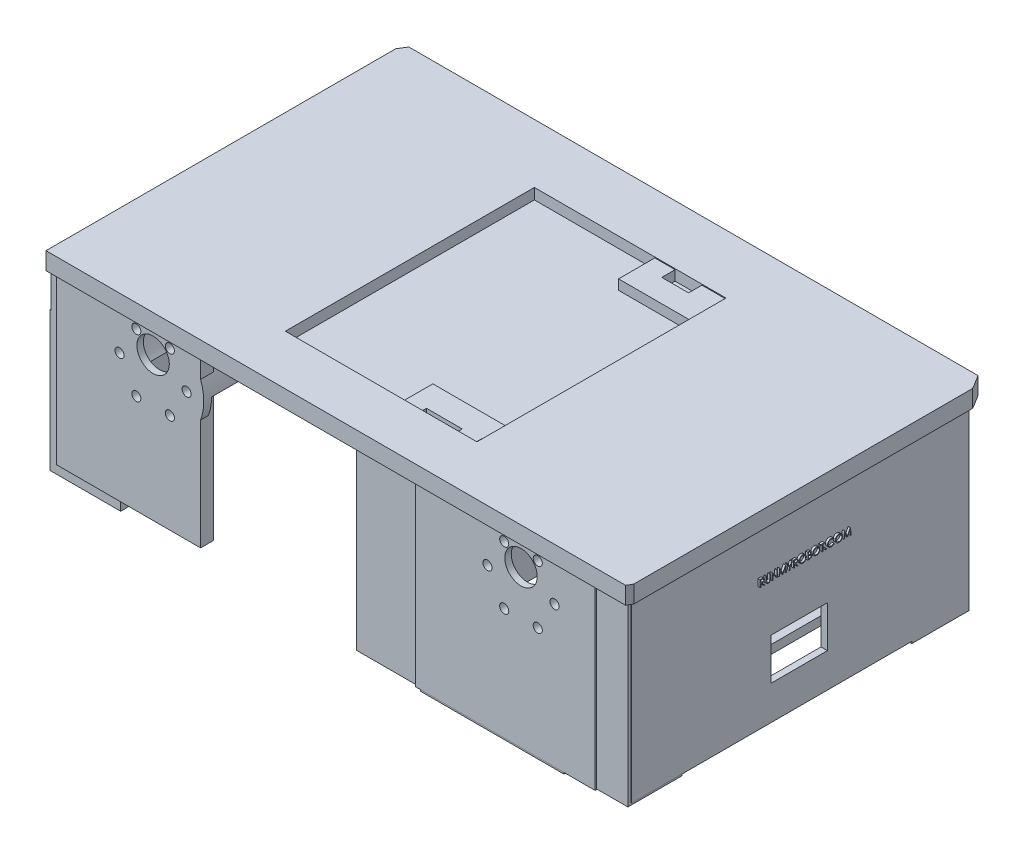
SolidWorks part; units mm, degrees
ref_plane "Front Plane" through (0, 0, 0) normal (0, 0, 1) x (1, 0, 0)
ref_plane "Top Plane" through (0, 0, 0) normal (0, 1, 0) x (1, 0, 0)
ref_plane "Right Plane" through (0, 0, 0) normal (1, 0, 0) x (0, 0, -1)
sketch "MotorHoldersSketch" plane through (0, 0, 0) normal (0, 0, 1) x (1, 0, 0)
  line L0 (0, 0) -> (170, 0) construction
  line L1 (0, 0) -> (0, 23.41) construction
  line L2 (170, 0) -> (170, 23.41) construction
  circle A0 centre (0, 0) radius 23.41
  circle A1 centre (170, 0) radius 23.41
ref_axis "MotorCenterAxis1" through (0, 0, 0) along (0, 0, 1)
ref_axis "MotorCenterAxis2" through (170, 0, 0) along (0, 0, 1)
extrude "MotorHolders" add sketch "MotorHoldersSketch" along normal blind 80 and the other way blind 80
sketch "Sketch3" plane through (0, 0, 0) normal (0, 0, 1) x (1, 0, 0)
  line L1 (1.9406, 21.133) -> (168.3435, 21.133)
  line L2 (1.9406, 21.133) -> (1.9406, 18.3155)
  line L3 (1.9406, 18.3155) -> (168.3435, 18.3155)
  line L4 (168.3435, 21.133) -> (168.3435, 18.3155)
sketch "Sketch4" plane through (0, 0, 0) normal (0, 1, 0) x (1, 0, 0)
  line L1 (221.2811, -76.3794) -> (-41.4939, -76.3794)
  line L2 (221.2811, -76.3794) -> (221.2811, 76.7331)
  line L3 (221.2811, 76.7331) -> (-41.4939, 76.7331)
  line L4 (-41.4939, -76.3794) -> (-41.4939, 76.7331)
extrude "Cut-Extrude1" cut sketch "Sketch4" against normal blind 26
ref_axis "Axis3" through (170, 0, 0) along (0, -1, 0)
sketch3d "ReferencePlanePosition"
  line L0 (170, 0, 0) -> (170, -34.8293, 0)
  line L1 (170, 0, 0) -> (170, -38.994, 0) construction
ref_plane "ReferencePlane" through (170, -34.8293, 0) normal (0, -1, 0) x (-1, 0, 0)
sketch "Sketch6" plane through (170, -34.8293, 0) normal (0, -1, 0) x (-1, 0, 0)
  line L1 (219.5858, 78.949) -> (145.1716, 78.949)
  line L2 (219.5858, 78.949) -> (219.5858, 65.5282)
  line L3 (219.5858, 65.5282) -> (145.1716, 65.5282)
  line L4 (145.1716, 78.949) -> (145.1716, 65.5282)
  line L5 (219.3147, -52.1095) -> (186.667, -52.1095)
  line L6 (219.3147, -52.1095) -> (219.3147, -78.2822)
  line L7 (219.3147, -78.2822) -> (186.667, -78.2822)
  line L8 (186.667, -52.1095) -> (186.667, -78.2822)
  line L9 (75.6651, 77.8627) -> (19.9904, 77.8627)
  line L10 (75.6651, 77.8627) -> (75.6651, 40.7512)
  line L11 (75.6651, 40.7512) -> (19.9904, 40.7512)
  line L12 (19.9904, 77.8627) -> (19.9904, 40.7512)
  line L13 (76.5596, -44.1716) -> (20.0852, -44.1716)
  line L14 (76.5596, -44.1716) -> (76.5596, -79.4437)
  line L15 (76.5596, -79.4437) -> (20.0852, -79.4437)
  line L16 (20.0852, -44.1716) -> (20.0852, -79.4437)
  line L17 (213.765, 73.0364) -> (192.9548, 73.0364)
  line L18 (213.765, 73.0364) -> (213.765, 71.0153)
  line L19 (213.765, 71.0153) -> (192.9548, 71.0153)
  line L20 (192.9548, 73.0364) -> (192.9548, 71.0153)
  line L21 (41.3552, 69.1777) -> (28.5109, 69.1777)
  line L22 (41.3552, 69.1777) -> (41.3552, 50.8413)
  line L23 (41.3552, 50.8413) -> (28.5109, 50.8413)
  line L24 (28.5109, 69.1777) -> (28.5109, 50.8413)
  line L25 (43.3068, -72.8101) -> (32.1723, -72.8101)
  line L26 (43.3068, -72.8101) -> (43.3068, -54.7747)
  line L27 (43.3068, -54.7747) -> (32.1723, -54.7747)
  line L28 (32.1723, -72.8101) -> (32.1723, -54.7747)
  line L29 (211.9411, -70.4881) -> (201.0982, -70.4881)
  line L30 (211.9411, -70.4881) -> (211.9411, -60.1404)
  line L31 (211.9411, -60.1404) -> (201.0982, -60.1404)
  line L32 (201.0982, -70.4881) -> (201.0982, -60.1404)
  line L37 (66.2772, 51.3198) -> (53.8697, 51.3198)
  line L38 (66.2772, 51.3198) -> (66.2772, 67.7632)
  line L39 (66.2772, 67.7632) -> (53.8697, 67.7632)
  line L40 (53.8697, 51.3198) -> (53.8697, 67.7632)
  line L45 (68.2481, -69.8638) -> (51.7107, -69.8638)
  line L46 (68.2481, -69.8638) -> (68.2481, -55.4273)
  line L47 (68.2481, -55.4273) -> (51.7107, -55.4273)
  line L48 (51.7107, -69.8638) -> (51.7107, -55.4273)
  line L49 (-20.7001, -79.4437) -> (-48.8506, -79.4437)
  line L50 (-20.7001, -79.4437) -> (-20.7001, -54.5097)
  line L51 (-20.7001, -54.5097) -> (-48.8506, -54.5097)
  line L52 (-48.8506, -79.4437) -> (-48.8506, -54.5097)
  line L53 (-18.3873, 77.8627) -> (-49.0581, 77.8627)
  line L54 (-18.3873, 77.8627) -> (-18.3873, 51.5325)
  line L55 (-18.3873, 51.5325) -> (-49.0581, 51.5325)
  line L56 (-49.0581, 77.8627) -> (-49.0581, 51.5325)
  line L57 (-41.8141, -72.8101) -> (-31.6362, -72.8101)
  line L58 (-41.8141, -72.8101) -> (-41.8141, -62.9794)
  line L59 (-41.8141, -62.9794) -> (-31.6362, -62.9794)
  line L60 (-31.6362, -72.8101) -> (-31.6362, -62.9794)
  line L61 (-31.6362, 69.1777) -> (-41.5347, 69.1777)
  line L62 (-31.6362, 69.1777) -> (-31.6362, 58.5421)
  line L63 (-31.6362, 58.5421) -> (-41.5347, 58.5421)
  line L64 (-41.5347, 69.1777) -> (-41.5347, 58.5421)
extrude "PowerBankHolders" add sketch "Sketch6" along normal blind 30 and the other way blind 59 separate body
sketch3d "3DSketch3"
  line L0 (170, 0, 0) -> (170, -64.5, 0) construction
ref_plane "Plane2" through (170, -64.5, 0) normal (0, -1, 0) x (-1, 0, 0)
sketch "Sketch7" plane through (170, -64.5, 0) normal (0, -1, 0) x (-1, 0, 0)
  line L1 (-9.5047, -80.801) -> (181.32, -80.801)
  line L2 (-9.5047, -80.801) -> (-9.5047, 73.8662)
  line L3 (-9.5047, 73.8662) -> (181.32, 73.8662)
  line L4 (181.32, -80.801) -> (181.32, 73.8662)
  line L5 (151.8712, -54.3972) -> (26.5361, -54.3972)
  line L6 (151.8712, -54.3972) -> (151.8712, 46.2413)
  line L7 (151.8712, 46.2413) -> (26.5361, 46.2413)
  line L8 (26.5361, -54.3972) -> (26.5361, 46.2413)
ref_point "Point1"
ref_point "Point2"
sketch3d "3DSketch11"
  line L0 (0, 0, -80) -> (170, 0, 80) construction
  point P4 (85, 0, 0)
sketch "MotorHolderExtrudeSketch" plane through (0, 0, 0) normal (0, 0, 1) x (1, 0, 0)
  circle A0 centre (170, 0) radius 20.415
  circle A1 centre (0, 0) radius 20.415
  circle A3 centre (0, 0) radius 23.41 construction
  circle A4 centre (170, 0) radius 23.41 construction
ref_point "TopOfMotors"
ref_plane "TangentToTopOfMotors" through (0, -20.415, 0) normal (0, 1, 0) x (1, 0, 0)
ref_axis "Axis4" through (85, 0, 0) along (0, -1, 0)
ref_plane "BottomOfPowerBankRegion" through (0, -20.425, 0) normal (0, 1, 0) x (1, 0, 0)
sketch "Sketch11" plane through (0, -20.425, 0) normal (0, 1, 0) x (1, 0, 0)
  line L0 (-18.9327, 3.7419) -> (188.9327, -3.7419) construction
  line L5 (-18.9327, -64.7581) -> (-18.9327, 72.2419)
  line L6 (188.9327, 63.7581) -> (188.9327, -71.2419)
  line L7 (188.9327, -71.2419) -> (-18.9327, -64.7581)
  line L8 (188.9327, 63.7581) -> (-18.9327, 72.2419)
  circle A0 centre (85, 0) radius 104 construction
ref_point "CenterAtBottomOfPowerBank"
ref_plane "TopOfPowerBankPlane" through (0, -54.425, 0) normal (0, 1, 0) x (1, 0, 0)
sketch "Sketch13" plane through (0, -54.425, 0) normal (0, 1, 0) x (1, 0, 0)
  line L1 (-19.4498, 72.5454) -> (166.1636, 72.5454)
  line L2 (-19.4498, 72.5454) -> (-19.4498, -78.2051)
  line L3 (-19.4498, -78.2051) -> (166.1636, -78.2051)
  line L4 (166.1636, 72.5454) -> (166.1636, -78.2051)
  line L5 (19.3173, -49.583) -> (137.9607, -49.583)
  line L6 (19.3173, -49.583) -> (19.3173, -21.0549)
  line L7 (19.3173, -21.0549) -> (137.9607, -21.0549)
  line L8 (137.9607, -49.583) -> (137.9607, -21.0549)
  line L9 (19.3173, 56.6778) -> (137.9607, 56.6778)
  line L10 (19.3173, 56.6778) -> (19.3173, 36.3234)
  line L11 (19.3173, 36.3234) -> (137.9607, 36.3234)
  line L12 (137.9607, 56.6778) -> (137.9607, 36.3234)
  line L13 (19.3173, 18.3186) -> (137.9607, 18.3186)
  line L14 (19.3173, 18.3186) -> (19.3173, -7.3615)
  line L15 (19.3173, -7.3615) -> (137.9607, -7.3615)
  line L16 (137.9607, 18.3186) -> (137.9607, -7.3615)
sketch "Sketch15" plane through (150.0096, 0, 0) normal (1, 0, 0) x (0, 0, -1)
  line L1 (72.5313, -25.7765) -> (45.7099, -25.7765)
  line L2 (72.5313, -25.7765) -> (72.5313, -24.2242)
  line L3 (72.5313, -24.2242) -> (45.7099, -24.2242)
  line L4 (45.7099, -25.7765) -> (45.7099, -24.2242)
extrude "PowerBankCut" cut sketch "Sketch11" against normal blind 64
ref_plane "Plane6" through (0, 0, 0) normal (0, 0, 1) x (1, 0, 0)
sketch "MotorGeometry1" plane through (0, 0, 0) normal (0, 0, 1) x (1, 0, 0)
  line L0 (170, 0) -> (170, -13.42)
  line L1 (170, 0) -> (170, -34.8293) construction
  line L2 (170, -13.42) -> (162.25, -13.42) construction
  line L3 (170, -13.42) -> (177.75, -13.42) construction
  line L4 (170, -13.42) -> (170, 7) construction
  line L5 (170, 0) -> (185.5, 0) construction
  line L6 (170, 0) -> (154.5, 0) construction
  line L7 (170, 0) -> (170, 13.42) construction
  line L8 (170, 0) -> (170, 23.41) construction
  line L9 (170, 13.42) -> (177.75, 13.42) construction
  line L10 (170, 13.42) -> (162.25, 13.42)
ref_axis "BoltAxisA" through (185.5, 0, 0) along (0, 0, 1)
ref_axis "BoltAxisB" through (177.75, -13.42, 0) along (0, 0, 1)
ref_axis "BoltAxisC" through (162.25, -13.42, 0) along (0, 0, 1)
ref_axis "BoltAxisD" through (154.5, 0, 0) along (0, 0, 1)
ref_axis "BoltAxisE" through (162.25, 13.42, 0) along (0, 0, 1)
ref_axis "BoltAxisF" through (177.75, 13.42, 0) along (0, 0, 1)
ref_point "Point6"
ref_point "Point7"
ref_point "Point8"
ref_point "Point9"
ref_point "Point10"
ref_point "Point11"
ref_point "Point12"
ref_point "Point13"
ref_point "Point14"
ref_point "Point15"
ref_point "Point16"
ref_point "Point17"
ref_plane "Plane7" through (0, 0, 0) normal (0, 0, 1) x (1, 0, 0)
sketch "MotorGeometry2" plane through (0, 0, 0) normal (0, 0, 1) x (1, 0, 0)
  line L0 (0, 0) -> (0, -13.42) construction
  line L1 (0, -13.42) -> (7.75, -13.42) construction
  line L2 (0, -13.42) -> (-7.75, -13.42) construction
  line L3 (0, 0) -> (0, 13.42)
  line L4 (0, -13.42) -> (0, 7) construction
  line L5 (0, 13.42) -> (7.75, 13.42) construction
  line L6 (0, 13.42) -> (-7.75, 13.42) construction
  line L7 (0, 0) -> (15.5, 0) construction
  line L8 (0, 0) -> (-15.5, 0) construction
  line L9 (0, 0) -> (0, 23.41) construction
ref_axis "Axis11" through (15.5, 0, 0) along (0, 0, 1)
ref_axis "Axis12" through (7.75, 13.42, 0) along (0, 0, 1)
ref_axis "Axis13" through (-7.75, 13.42, 0) along (0, 0, 1)
ref_axis "Axis14" through (-15.5, 0, 0) along (0, 0, 1)
ref_axis "Axis15" through (-7.75, -13.42, 0) along (0, 0, 1)
ref_axis "Axis16" through (7.75, -13.42, 0) along (0, 0, 1)
ref_point "Point18"
ref_point "Point19"
ref_point "Point20"
ref_point "Point21"
ref_point "Point22"
ref_point "Point23"
ref_point "Point24"
ref_point "Point25"
ref_point "Point26"
ref_point "Point27"
ref_point "Point28"
ref_point "Point29"
ref_plane "BottomPlane" through (0, 19.575, 0) normal (0, 1, 0) x (1, 0, 0)
ref_axis "OutputShaftReference1" through (0, 7, 0) along (0, 0, 1)
ref_point "Point35"
ref_axis "OutputShaftReference2" through (170, 7, 0) along (0, 0, 1)
sketch "Sketch21" plane through (0, 19.575, 0) normal (0, 1, 0) x (1, 0, 0)
  line L0 (219.6842, -79.5488) -> (-50.341, -79.5488) construction
  line L1 (-50.341, -79.5488) -> (-50.341, 79.7899) construction
  line L2 (-50.341, 79.7899) -> (219.6842, 79.7899) construction
  line L3 (219.6842, 79.7899) -> (219.6842, -79.5488) construction
  line L4 (127.2472, -57.5918) -> (127.2472, 57.4773)
  line L5 (127.2472, 57.4773) -> (38.7099, 57.4773)
  line L6 (38.7099, 57.4773) -> (38.7099, -57.5918)
  line L7 (38.7099, -57.5918) -> (127.2472, -57.5918)
  circle A0 centre (85, 0) radius 156.3953
extrude "BottomPlate" add sketch "Sketch21" along normal blind 5 and the other way blind 3
ref_plane "HoleReferencePlane1" through (0, 0, 80) normal (0, 0, 1) x (1, 0, 0)
ref_point "OutputShaftPosition3"
ref_point "OutputShaftPosition1"
sketch "Sketch23" plane through (0, 0, 80) normal (0, 0, 1) x (1, 0, 0)
  line L1 (21.9586, -59.3229) -> (-44.5901, -59.3229)
  line L2 (21.9586, -59.3229) -> (21.9586, 21.8402)
  line L3 (21.9586, 21.8402) -> (-44.5901, 21.8402)
  line L4 (-44.5901, -59.3229) -> (-44.5901, 21.8402)
  line L5 (121.3218, 21.8402) -> (204.258, 21.8402)
  line L6 (121.3218, 21.8402) -> (121.3218, -65.2231)
  line L7 (121.3218, -65.2231) -> (204.258, -65.2231)
  line L8 (204.258, 21.8402) -> (204.258, -65.2231)
extrude "MotorMountingSupport1" add sketch "Sketch23" against normal blind 6
ref_plane "HoleReferencePlane2" through (0, 0, -80) normal (0, 0, -1) x (-1, 0, 0)
ref_point "OutputShaftPosition4"
ref_point "OutputShaftPosition2"
sketch "Sketch24" plane through (0, 0, -80) normal (0, 0, -1) x (-1, 0, 0)
  line L1 (-202.1905, -67.1257) -> (-139.5471, -67.1257)
  line L2 (-202.1905, -67.1257) -> (-202.1905, 19.2374)
  line L3 (-202.1905, 19.2374) -> (-139.5471, 19.2374)
  line L4 (-139.5471, -67.1257) -> (-139.5471, 19.2374)
  line L5 (-24.3642, -64.1521) -> (29.5505, -64.1521)
  line L6 (-24.3642, -64.1521) -> (-24.3642, 22.5226)
  line L7 (-24.3642, 22.5226) -> (29.5505, 22.5226)
  line L8 (29.5505, -64.1521) -> (29.5505, 22.5226)
extrude "MotorMountingSuppor2" add sketch "Sketch24" against normal blind 6
sketch "Sketch17" plane through (0, 0, 80) normal (0, 0, 1) x (1, 0, 0)
  circle A0 centre (185.5, 0) radius 2.1
  circle A1 centre (177.75, -13.42) radius 2.1
  circle A2 centre (162.25, -13.42) radius 2.1
  circle A3 centre (154.5, 0) radius 2.1
  circle A4 centre (162.25, 13.42) radius 2.1
  circle A5 centre (177.75, 13.42) radius 2.1
  circle A6 centre (170, 7) radius 7.5
extrude "MotorHoles1" cut sketch "Sketch17" against normal blind 31.5
sketch "Sketch19" plane through (0, 0, -80) normal (0, 0, -1) x (-1, 0, 0)
  circle A0 centre (-185.5, 0) radius 2.1
  circle A1 centre (-177.75, -13.42) radius 2.1
  circle A2 centre (-162.25, -13.42) radius 2.1
  circle A3 centre (-154.5, 0) radius 2.1
  circle A4 centre (-162.25, 13.42) radius 2.1
  circle A5 centre (-177.75, 13.42) radius 2.1
  circle A6 centre (-170, 7) radius 7.5
sketch "BoltHolesSketch3" plane through (0, 0, 80) normal (0, 0, 1) x (1, 0, 0)
  circle A0 centre (7.75, -13.42) radius 2.1
  circle A1 centre (15.5, 0) radius 2.1
  circle A2 centre (7.75, 13.42) radius 2.1
  circle A3 centre (-7.75, 13.42) radius 2.1
  circle A4 centre (-15.5, 0) radius 2.1
  circle A5 centre (-7.75, -13.42) radius 2.1
  circle A6 centre (0, 7) radius 7.5
extrude "Cut-Extrude4" cut sketch "Sketch19" against normal blind 30
extrude "MotorHoles3" cut sketch "BoltHolesSketch3" against normal blind 31.5
sketch "BoltHolesSketch4" plane through (0, 0, -80) normal (0, 0, -1) x (-1, 0, 0)
  circle A0 centre (-15.5, 0) radius 2.1
  circle A1 centre (-7.75, 13.42) radius 2.1
  circle A2 centre (7.75, 13.42) radius 2.1
  circle A3 centre (15.5, 0) radius 2.1
  circle A4 centre (7.75, -13.42) radius 2.1
  circle A5 centre (-7.75, -13.42) radius 2.1
  circle A6 centre (0, 7) radius 7.5
extrude "MotorHoles4" cut sketch "BoltHolesSketch4" against normal blind 15
ref_plane "Front" through (219.0581, 0, 0) normal (1, 0, 0) x (0, 0, -1)
sketch "Sketch29" plane through (219.0581, 0, 0) normal (1, 0, 0) x (0, 0, -1)
  line L1 (76.6955, -63.9254) -> (-77.9397, -63.9254)
  line L2 (76.6955, -63.9254) -> (76.6955, 20.2062)
  line L3 (76.6955, 20.2062) -> (-77.9397, 20.2062)
  line L4 (-77.9397, -63.9254) -> (-77.9397, 20.2062)
  line L5 (-13.4507, -48.1531) -> (12.5493, -48.1531)
  line L6 (-13.4507, -48.1531) -> (-13.4507, -28.9404)
  line L7 (-13.4507, -28.9404) -> (12.5493, -28.9404)
  line L8 (12.5493, -48.1531) -> (12.5493, -28.9404)
extrude "Boss-Extrude8" add sketch "Sketch29" against normal blind 3
ref_plane "RaspberryPiBasePlane" through (0, 16.575, 0) normal (0, -1, 0) x (-1, 0, 0)
sketch "Sketch27" plane through (0, 16.575, 0) normal (0, -1, 0) x (-1, 0, 0)
  line L1 (31.6337, 64.5517) -> (-194.8264, 64.5517)
  line L2 (31.6337, 64.5517) -> (31.6337, -65.4335)
  line L3 (31.6337, -65.4335) -> (-194.8264, -65.4335)
  line L4 (-194.8264, 64.5517) -> (-194.8264, -65.4335)
extrude "Boss-Extrude6" add sketch "Sketch27" against normal blind 3
ref_plane "Plane12" through (0, -64.8293, 0) normal (0, -1, 0) x (-1, 0, 0)
sketch "Sketch28" plane through (0, -64.8293, 0) normal (0, -1, 0) x (-1, 0, 0)
  line L1 (-189.3897, -79.549) -> (-123.0026, -79.549)
  line L2 (-189.3897, -79.549) -> (-189.3897, 78.1499)
  line L3 (-189.3897, 78.1499) -> (-123.0026, 78.1499)
  line L4 (-123.0026, -79.549) -> (-123.0026, 78.1499)
extrude "Boss-Extrude7" add sketch "Sketch28" along normal blind 1.5 and the other way blind 2.5
extrude "MotorHolderCut" cut sketch "MotorHolderExtrudeSketch" against normal blind 77 and the other way blind 77
sketch "Sketch31" plane through (219.0581, 0, 0) normal (1, 0, 0) x (0, 0, -1)
  text T0 "RUNMYROBOT.COM"
extrude "Boss-Extrude9" add sketch "Sketch31" along normal blind 1
sketch "Sketch32" plane through (0, 19.575, 0) normal (0, 1, 0) x (1, 0, 0)
  line L1 (-48.8137, 84.6887) -> (220.392, 84.6887)
  line L2 (-48.8137, 84.6887) -> (-48.8137, -80.6635)
  line L3 (-48.8137, -80.6635) -> (220.392, -80.6635)
  line L4 (220.392, 84.6887) -> (220.392, -80.6635)
  line L5 (283.5566, -218.7268) -> (-136.4889, -218.7268)
  line L8 (-136.4889, -218.7268) -> (-136.4889, 206.3198)
  line L10 (283.5566, 206.3198) -> (283.5566, -218.7268)
  line L13 (283.5566, 206.3198) -> (-136.4889, 206.3198)
extrude "Cut-Extrude5" cut sketch "Sketch32" along normal blind 20 and the other way blind 20
sketch "Sketch35" plane through (0, 0, -84.6887) normal (0, 0, -1) x (-1, 0, 0)
  line L0 (69.0502, 16.3777) -> (-36.4474, 27.6206)
  line L1 (-36.4474, 27.6206) -> (71.6404, 26.1593)
  line L2 (69.0502, 16.3777) -> (71.6404, 26.1593)
  line L3 (-223.8844, 30.8145) -> (-223.8844, 17.5678)
  line L4 (-223.8844, 17.5678) -> (-116.0163, 30.8145)
  line L5 (-116.0163, 30.8145) -> (-223.8844, 30.8145)
sketch "Sketch36" plane through (-49.3147, 0, 0) normal (-1, 0, 0) x (0, 0, 1)
  line L0 (52.1095, -64.8293) -> (52.1095, -44.3593) construction
  line L1 (52.1095, -0.425) -> (52.1095, -64.8293) construction
  circle A0 centre (52.1095, -44.3593) radius 7.4588
extrude "Cut-Extrude6" cut sketch "Sketch36" against normal blind 40
sketch "Sketch37" plane through (0, -20.425, 0) normal (0, -1, 0) x (1, 0, 0)
  line L1 (144.416, -35.6729) -> (89.0759, -35.6729)
  line L2 (144.416, -35.6729) -> (144.416, -65.4438)
  line L3 (144.416, -65.4438) -> (89.0759, -65.4438)
  line L4 (89.0759, -35.6729) -> (89.0759, -65.4438)
extrude "Cut-Extrude7" cut sketch "Sketch37" against normal blind 36
